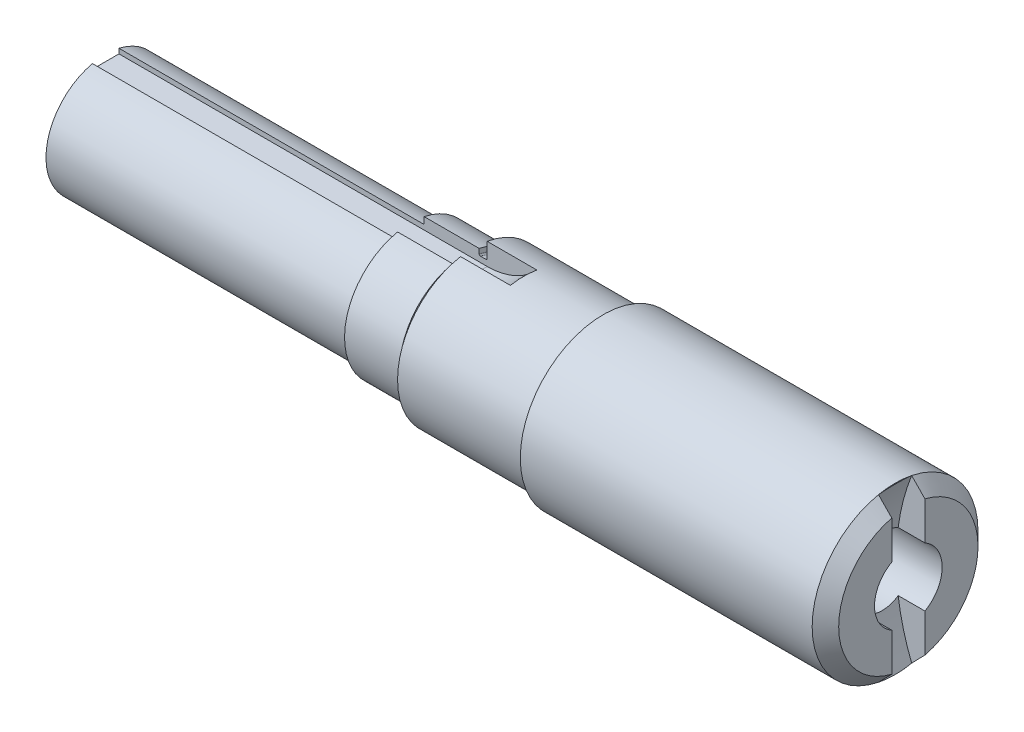
SolidWorks part; units mm, degrees
ref_plane "Plan de face" through (0, 0, 0) normal (0, 0, 1) x (1, 0, 0)
ref_plane "Plan de dessus" through (0, 0, 0) normal (0, 1, 0) x (1, 0, 0)
ref_plane "Plan de droite" through (0, 0, 0) normal (1, 0, 0) x (0, 0, -1)
sketch "Esquisse1" plane through (0, 0, 0) normal (0, 0, 1) x (1, 0, 0)
  line L0 (-54.5395, 0) -> (142.3857, 0) construction
  line L1 (0, 9) -> (0, 0)
  line L2 (0, 9) -> (46.0083, 9)
  line L3 (46.0083, 9) -> (46.0083, 10)
  line L4 (55.5, 11.5) -> (75, 11.5)
  line L5 (121, 12.5) -> (121, 0)
  line L6 (0, 0) -> (121, 0)
  line L7 (75, 11.5) -> (75, 12.5)
  line L8 (75, 12.5) -> (121, 12.5)
  line L9 (46.0083, 10) -> (55.5, 10)
  line L10 (55.5, 10) -> (55.5, 11.5)
  dimension "D1" = 12.5
  dimension "D2" = 11.5
  dimension "D3" = 46
  dimension "D4" = 19.5
  dimension "D5" = 121
  dimension "D6" = 9
  dimension "D7" = 10
revolve "Révolution1" add sketch "Esquisse1" angle 360 about L0
cosmetic thread "Représentation de filetage1" parameters "D2"=18
hole_wizard "Trou taraudé M121" positions "Esquisse6" profile "Esquisse7" tap size "M12" standard "ISO" end condition through all
sketch "Esquisse6" plane through (0, 0, 0) normal (-1, 0, 0) x (0, 0, 1)
  point P10 (0, 0)
sketch "Esquisse7" plane through (0, 0, 0) normal (0, 1, 0) x (0, 0, 1)
  line L0 (0, 0) -> (0, 121)
  line L1 (0, 121) -> (5.1, 121)
  line L2 (5.1, 121) -> (5.1, 0)
  line L5 (5.1, 0) -> (0, 0)
  line L11 (0, -6.35) -> (0, 107.95) construction
  dimension "Diamètre du trou pour taraudage jusqu'au prochain" = 10.2
  dimension "Profondeur du trou pour taraudage jusqu'au prochain" = 121
cosmetic thread "Filetage de perçage3" parameters "D1"=68, "D2"=12
sketch "Esquisse8" plane through (0, 0, 0) normal (-1, 0, 0) x (0, 0, 1)
  circle A0 centre (0, 0) radius 7
  dimension "D1" = 14
extrude "Enlèv. mat.-Extru.1" cut sketch "Esquisse8" against normal blind 20
chamfer "Chanfrein1" distance 1.9 angle 45 1 edges at (20, 0, 5.1)
sketch "Esquisse9" plane through (0, 0, 0) normal (-1, 0, 0) x (0, 0, 1)
  line L0 (0, 0) -> (0, 27.9136) construction
  line L1 (-2, 8.0408) -> (2, 8.0408)
  line L2 (2, 8.0408) -> (2, 13.7387)
  line L3 (-2, 8.0408) -> (-2, 13.5)
  line L4 (2, 13.5) -> (-2, 13.5) construction
  line L5 (-2, 13.5) -> (2, 13.7387)
  dimension "D1" = 4
extrude "Enlèv. mat.-Extru.2" cut sketch "Esquisse9" against normal blind 63
fillet "Congé1" radius 10 1 edges at (63, 8.0408, 0)
sketch "Esquisse10" plane through (0, 0, 0) normal (0, 0, 1) x (1, 0, 0)
  line L0 (121, -12.5) -> (121, 12.5) construction
  line L1 (0, 0) -> (130.6749, 0) construction
  circle A0 centre (150, 0) radius 33.3333
  dimension "D1" = 66.6667
  dimension "D2" = 29
chamfer "Chanfrein2" distance 2 angle 45 1 edges at (121, 0, 12.5)
extrude "Enlèv. mat.-Extru.3" cut sketch "Esquisse10" against normal mid plane 5
ref_plane "Plan1" through (-54.5395, 0, 0) normal (0, -1, 0) x (0, 0, 1)
sketch "Esquisse12" plane through (-54.5395, 0, 0) normal (0, -1, 0) x (0, 0, 1)
  line L0 (9.3061, -110.0395) -> (12, -110.0395)
  line L1 (12, -110.0395) -> (12, -108.8395)
  line L2 (12, -108.8395) -> (9.3061, -108.8395)
  line L3 (9.1061, -109.0395) -> (9.1061, -109.8395)
  line L4 (0, -50) -> (0, 50) construction
  line L5 (11.5, -110.0395) -> (-11.5, -110.0395) construction
  line L6 (11.5, -110.0395) -> (-11.5, -110.0395) construction
  arc A0 (9.1061, -109.8395) -> (9.3061, -110.0395) centre (9.3061, -109.8395) ccw
  arc A1 (9.1061, -109.0395) -> (9.3061, -108.8395) centre (9.3061, -109.0395) cw
  dimension "D1" = 0.2
  dimension "D2" = 0.2
  dimension "D3" = 1.2
  dimension "D4" = 0.8
revolve "Gorge pour ANSI B27.7 - 3AM1-20, Circlip Basique extérieur1" cut sketch "Esquisse12"
